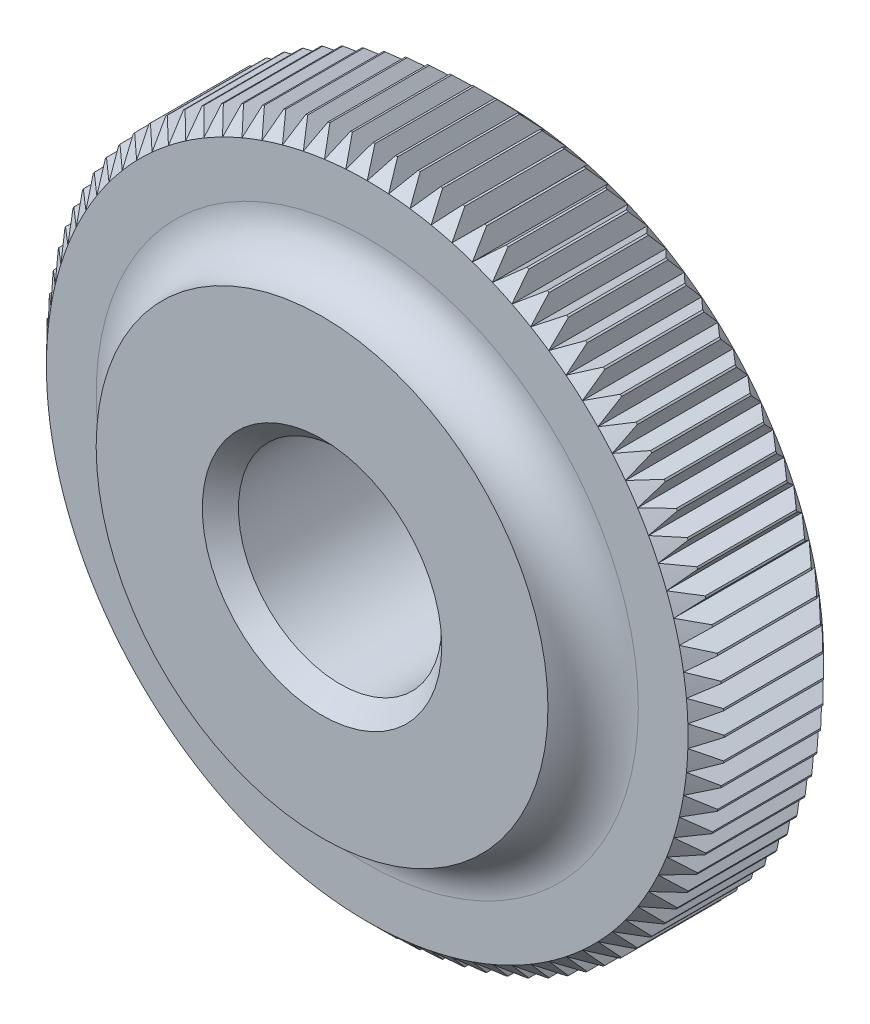
SolidWorks part; units mm, degrees
ref_plane "前视" through (0, 0, 0) normal (0, 0, 1) x (1, 0, 0)
ref_plane "上视" through (0, 0, 0) normal (0, 1, 0) x (1, 0, 0)
ref_plane "右视" through (0, 0, 0) normal (1, 0, 0) x (0, 0, -1)
sketch "Sketch1" plane through (0, 0, 0) normal (0, 0, 1) x (1, 0, 0)
  circle A0 centre (0, 0) radius 15
extrude "BaseNut" add sketch "Sketch1" against normal blind 6
sketch "Sketch2" plane through (2.2068, 1.9379, -6) normal (0, 0, -1) x (-1, 0, 0)
  circle A0 centre (2.2068, -1.9379) radius 10
  circle A1 centre (2.2068, -1.9379) radius 15 construction
  dimension "dw" = 20
extrude "Extrude1" add sketch "Sketch2" against normal blind 8
fillet "Fillet1" radius 2 1 edges at (10, 0, 0)
sketch "Sketch3" plane through (-1.1811, -0.1207, 2) normal (0, 0, 1) x (1, 0, 0)
  circle A0 centre (1.1811, 0.1207) radius 4.5
  circle A1 centre (1.1811, 0.1207) radius 10 construction
  dimension "D1" = 9
extrude "Hole1" cut sketch "Sketch3" against normal through all
cosmetic thread "ThreadCosmetic1" [suppressed] parameters "D2"=10
sketch "Sketch4" plane through (0, 0, 0) normal (0, 1, 0) x (1, 0, 0)
  line L0 (0, 2.6341) -> (0, -9.703) construction
  line L2 (4.5, 6) -> (5.4, 6)
  line L5 (5.4, 6) -> (4.5, 5.1)
  line L7 (4.5, 5.1) -> (4.5, 6)
  dimension "Da" = 10.8
  dimension "D2" = 45
revolve "EndChamfer" [suppressed] cut sketch "Sketch4" angle 360 about L0
chamfer "Chamfer1" distance 0.8 angle 45 2 edges at (15, 0, -6) (15, 0, 0)
sketch "Sketch5" plane through (0, 6, -6) normal (0, 0, -1) x (1, 0, 0)
  line L0 (-0.25, 20.9979) -> (-0.25, 20.1978) construction
  line L1 (0, 22.5643) -> (0, 11.3282) construction
  line L2 (0.25, 20.9979) -> (0.25, 20.1978) construction
  line L4 (-0.6928, 21.4) -> (0, 20.2)
  line L5 (0, 20.2) -> (0.6928, 21.4)
  line L6 (0.6928, 21.4) -> (-0.6928, 21.4)
  circle A0 centre (0, 6) radius 14.2 construction
  arc A1 (0.25, 20.1978) -> (-0.25, 20.1978) centre (0, 6) ccw construction
  arc A2 (0.25, 20.9979) -> (-0.25, 20.9979) centre (0, 6) ccw construction
  circle A4 centre (0, 21) radius 0.4 construction
  circle A5 centre (0, 6) radius 15 construction
  dimension "D2" = 0.5
extrude "Cut-Extrude1" cut sketch "Sketch5" against normal through all
pattern_circular "CirPattern1" count 94 over 360 about axis through (0, 0, -2.6341) along (0, 0, 1) of "Cut-Extrude1"
chamfer "Chamfer2" distance 0.8 angle 45 1 edges at (4.5, 0, 2)
sketch "Sketch7" plane through (0, 0, 0) normal (1, 0, 0) x (0, 0, -1)
  line L0 (13.2499, 0) -> (-8.3535, 0) construction
  line L1 (-0.95, -4) -> (-1.45, -4)
  line L2 (-1.45, -4) -> (-1.45, -4.5)
  line L3 (-1.45, -4.5) -> (-1.2, -4.933)
  line L4 (-1.2, -4.933) -> (-0.95, -4.5)
  line L5 (-0.95, -4.5) -> (-0.95, -4)
  line L6 (-1.2, -4.5) -> (-1.2, 4.5) construction
  dimension "D2" = 9
revolve "Cut-Revolve10" [suppressed] cut sketch "Sketch7" angle 360 about L0
pattern_linear "LPattern10" [suppressed] count 12 spacing 0.6 along (0, 0, -1) of bodies 107
equation "\"D2@Sketch5\" = \"dk@Sketch1\" / 30"
equation "\"D1@CirPattern1\" = int ( 3.14 / atn ( 2 * \"D2@Sketch5\" / \"dk@Sketch1\" )  ) "
equation "\"D1@Chamfer2\" = \"D1@Chamfer1\""
equation "\"D2@Sketch7\" = \"D1@Sketch3\""
equation "\"D1@Sketch7\" =  ( \"D2@ThreadCosmetic1\" - \"D1@Sketch3\" )  / 2"
equation "\"D3@LPattern10\" = \"D1@Sketch7\" * 1.2 "
equation "\"D1@LPattern10\" =\"m@Extrude1\" / \"D3@LPattern10\" - 1"
